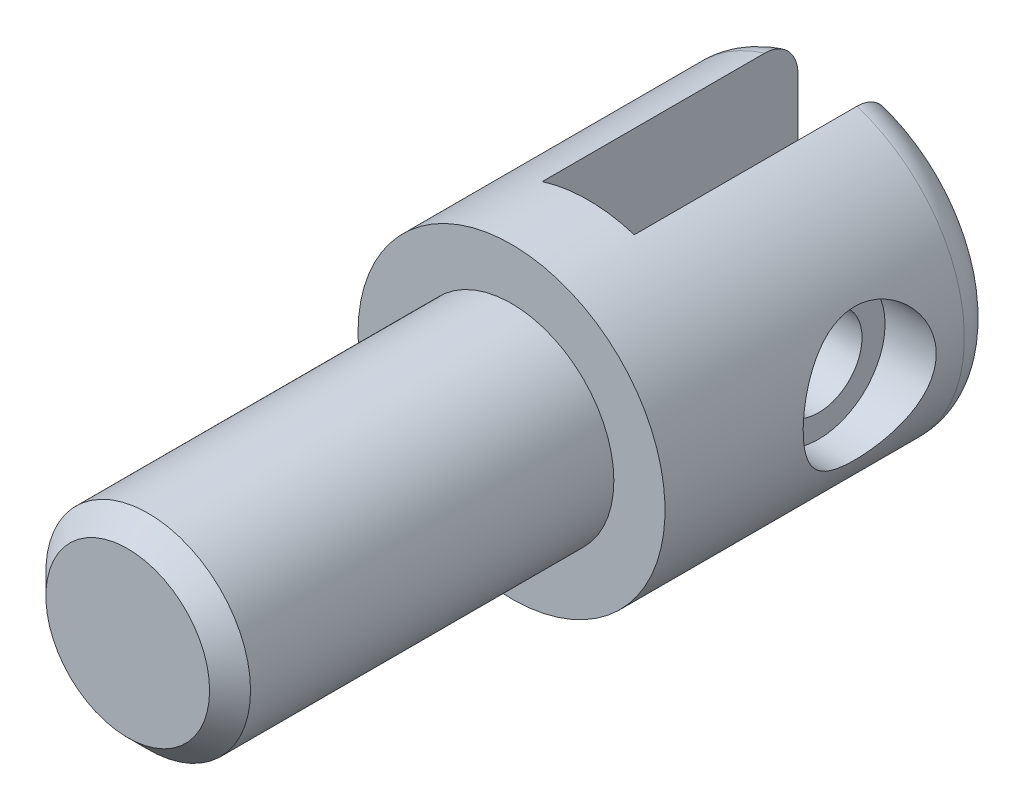
SolidWorks part; units mm, degrees
ref_plane "Plan1" through (0, 0, 0) normal (0, 0, 1) x (1, 0, 0)
ref_plane "Plan2" through (0, 0, 0) normal (0, 1, 0) x (1, 0, 0)
ref_plane "Plan3" through (0, 0, 0) normal (1, 0, 0) x (0, 0, -1)
ref_axis "Z Axis" through (0, 0, -50) along (0, 0, 1)
sketch "Esquisse1" plane through (0, 0, 0) normal (0, 1, 0) x (1, 0, 0)
  line L0 (0, 0) -> (0, 13) construction
  line L1 (0, 0) -> (6, 0)
  line L2 (0, 0) -> (0, 13)
  line L3 (0, 13) -> (4.7, 13)
  line L5 (6, 0) -> (6, 11.7)
  arc A0 (4.7, 13) -> (6, 11.7) centre (4.7, 11.7) cw
  dimension "D3" = 1.3
  dimension "D1" = 6
  dimension "D2" = 13
revolve "Base-Révolution" add sketch "Esquisse1" angle 360 about L0 reverse direction yes
sketch "Esquisse2" plane through (0, 0, -13) normal (0, 0, 1) x (1, 0, 0)
  line L0 (1.8, -5.7236) -> (1.8, 5.7236)
  line L1 (0, 0) -> (1.8, 1.0392) construction
  line L2 (1, 0) -> (1.8, 0) construction
  line L5 (0, 0) -> (0, 3) construction
  line L6 (-1.8, -5.7236) -> (-1.8, 5.7236)
  circle A0 centre (0, 0) radius 6 construction
  arc A1 (1.8, 5.7236) -> (-1.8, 5.7236) centre (0, 0) ccw
  arc A2 (-1.8, -5.7236) -> (1.8, -5.7236) centre (0, 0) ccw
  dimension "D2" = 30
  dimension "D1" = 3.6
sketch "Esquisse3" plane through (0, 0, 0) normal (0, 1, 0) x (1, 0, 0)
  line L1 (0, 0) -> (0, -15) construction
  line L2 (0, 0) -> (4, 0)
  line L3 (0, 0) -> (0, -15)
  line L4 (0, -15) -> (4, -15)
  line L6 (4, 0) -> (4, -15)
  dimension "D1" = 15
  dimension "D2" = 4
revolve "Boss.-Révol.1" add sketch "Esquisse3" angle 360 about L1 reverse direction yes
sketch "Esquisse4" plane through (0, 0, 0) normal (0, 1, 0) x (1, 0, 0)
  line L0 (3.39, -15.061) -> (3.39, -14.939)
  line L1 (-4, -15) -> (4, -15) construction
  line L2 (3.39, -14.939) -> (4.061, -14.5516)
  line L3 (3.39, -15.061) -> (4.061, -15.4484)
  line L4 (4.061, -14.5516) -> (4.061, -15.4484)
  line L5 (4, -15) -> (4, 0) construction
  point P4 (4, -15)
  dimension "D2" = 0.061
  dimension "D3" = 0.061
  dimension "D4" = 0.671
  dimension "D5" = 60
  dimension "D1" = 0.61
  dimension "D6" = 60
chamfer "Chanfrein1" distance 0.8 angle 45 1 edges at (4, 0, 15)
sketch "Esquisse5" plane through (0, 0, 15) normal (0, 0, 1) x (1, 0, 0)
  circle A0 centre (0, 0) radius 4 construction
  circle A1 centre (0, 0) radius 4
curve "Hélice1" pitch 1 height 15 turns 15
sweep "Enlèvement de matière-Balayage1" [suppressed] cut profiles "Esquisse4" path "Hélice1"
extrude "Enlèv. mat.-Extru.3" cut sketch "Esquisse2" along normal blind 10
ref_plane "Plan4" through (7, 0, 0) normal (1, 0, 0) x (0, 0, -1)
hole_wizard "Chambrage pour vis à tête hexagonale M31" positions "Esquisse7" profile "Esquisse6" counterbore size "M3" standard "ISO"
sketch "Esquisse7" plane through (7, 0, 0) normal (1, 0, 0) x (0, 0, -1)
  line L0 (13, -4.3417) -> (13, 4.3417) construction
  line L1 (9.2156, 0) -> (16.6687, 0) construction
  point P0 (8, 0)
  dimension "D1" = 5
sketch "Esquisse6" plane through (7, 0, -8) normal (0, 1, 0) x (0, 0, -1)
  line L0 (0, 0) -> (0, 9.0215)
  line L1 (0, 9.0215) -> (1.7, 8)
  line L2 (1.7, 8) -> (1.7, 3)
  line L3 (1.7, 3) -> (2.6, 3)
  line L4 (2.6, 3) -> (2.6, 0)
  line L5 (2.6, 0) -> (0, 0)
  line L10 (0, 9.0215) -> (-1.7, 8) construction
  line L11 (0, -6.35) -> (0, 107.95) construction
  dimension "Diamètre du perçage" = 3.4
  dimension "Profondeur du perçage" = 8
  dimension "Diamètre du chambrage" = 5.2
  dimension "Profondeur du chambrage" = 3
  dimension "Angle de pointe" = 118
hole_wizard "Trou taraudé M31" positions "Esquisse9" profile "Esquisse8" tap size "M3" standard "ISO" end condition through all
sketch "Esquisse9" plane through (-1.8, 0, 0) normal (1, 0, 0) x (0, 0, -1)
  point P0 (8, 0)
sketch "Esquisse8" plane through (-1.8, 0, -8) normal (0, 1, 0) x (0, 0, -1)
  line L0 (0, 0) -> (0, 4.2)
  line L1 (0, 4.2) -> (1.25, 4.2)
  line L2 (1.25, 4.2) -> (1.25, 0)
  line L5 (1.25, 0) -> (0, 0)
  line L11 (0, -6.35) -> (0, 107.95) construction
  dimension "Diamètre du trou pour taraudage jusqu'au prochain" = 2.5
  dimension "Profondeur du trou pour taraudage jusqu'au prochain" = 4.2
cosmetic thread "Filetage de perçage1" parameters "D2"=3
equation "\"D3@Esquisse1\"=\"D2@Esquisse1\"/10"
equation "\"D1@Chanfrein1\"=\"D2@Esquisse3\"*0.2"
equation "\"D3@Esquisse4\"=0.1*\"D1@Esquisse4\""
equation "\"D4@Esquisse4\"=1.1*\"D1@Esquisse4\""
equation "\"D2@Esquisse4\"=0.1*\"D1@Esquisse4\""
equation "\"D1@Esquisse4\"=0.61*\"D4@Hélice1\""
